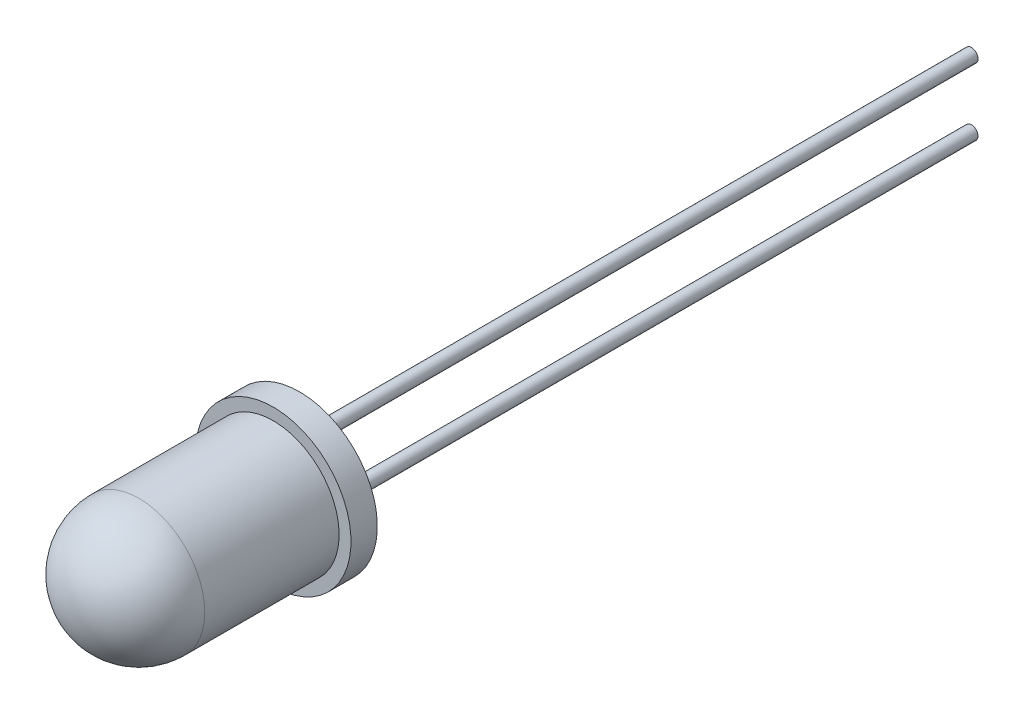
SolidWorks part; units mm, degrees
ref_plane "Спереди" through (0, 0, 0) normal (0, 0, 1) x (1, 0, 0)
ref_plane "Сверху" through (0, 0, 0) normal (0, 1, 0) x (1, 0, 0)
ref_plane "Справа" through (0, 0, 0) normal (1, 0, 0) x (0, 0, -1)
sketch "Эскиз1" plane through (0, 0, 0) normal (0, 0, 1) x (1, 0, 0)
  circle A0 centre (0, 0) radius 2.5
  dimension "D1" = 5
extrude "Бобышка-Вытянуть1" add sketch "Эскиз1" along normal blind 7.6
fillet "Скругление1" radius 2.5 1 edges at (2.5, 0, 7.6)
sketch "Эскиз2" plane through (0, 0, 0) normal (0, 0, -1) x (-1, 0, 0)
  circle A0 centre (0, 0) radius 2.95
  dimension "D1" = 5.9
extrude "Бобышка-Вытянуть2" add sketch "Эскиз2" along normal blind 1
sketch "Эскиз3" plane through (0, 0, -1) normal (0, 0, -1) x (-1, 0, 0)
  circle A0 centre (0, 0) radius 2.5
  dimension "D1" = 5
extrude "Бобышка-Вытянуть3" add sketch "Эскиз3" along normal blind 0.5
chamfer "Фаска1" distance 0.5 angle 45 1 edges at (-2.5, 0, -1.5)
sketch "Эскиз4" plane through (0, 0, -1.5) normal (0, 0, -1) x (-1, 0, 0)
  line L0 (0, -1.27) -> (0, 1.27) construction
  circle A0 centre (0, 1.27) radius 0.25
  circle A1 centre (0, -1.27) radius 0.25
  point P6 (0, 0)
  dimension "D1" = 2.54
extrude "Бобышка-Вытянуть4" add sketch "Эскиз4" along normal blind 25
